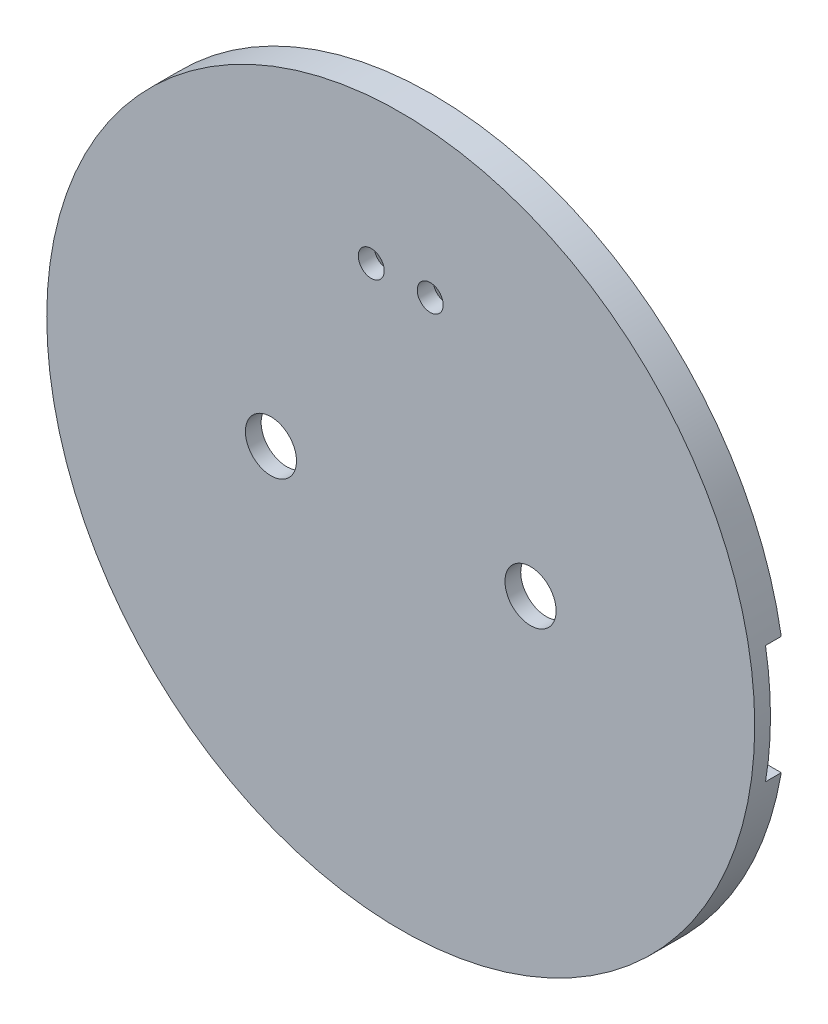
SolidWorks part; units mm, degrees
ref_plane "Plano frontal" through (0, 0, 0) normal (0, 0, 1) x (1, 0, 0)
ref_plane "Plano superior" through (0, 0, 0) normal (0, 1, 0) x (1, 0, 0)
ref_plane "Plano direito" through (0, 0, 0) normal (1, 0, 0) x (0, 0, -1)
sketch "Esboço1" plane through (0, 0, 0) normal (0, 0, 1) x (1, 0, 0)
  circle A0 centre (0, 0) radius 90
base flange "Flange-base2" sketch "Esboço1" thickness 8 reverse thickness direction no parameters "D1"=4
sketch "Esboço12" plane through (0, 0, -8) normal (0, 0, -1) x (-1, 0, 0)
  line L5 (-88.7412, 15) -> (88.7412, 15)
  line L6 (-88.7412, -15) -> (88.7412, -15)
  circle A0 centre (0, 0) radius 90 construction
  arc A1 (-88.7412, 15) -> (-88.7412, -15) centre (0, 0) ccw
  arc A2 (88.7412, 15) -> (88.7412, -15) centre (0, 0) cw
  point P0 (0, 0)
  point P4 (0, 0)
  point P11 (0, -15)
  point P14 (0, 15)
extrude "Corte-extrusão3" cut sketch "Esboço12" against normal blind 4 normal cut yes
sketch "Esboço13" plane through (0, 0, -4) normal (0, 0, -1) x (-1, 0, 0)
  circle A0 centre (33, 0) radius 6.5 construction
  circle A1 centre (-33, 0) radius 6.5 construction
  circle A2 centre (33, 0) radius 6.5
  circle A3 centre (-33, 0) radius 6.5
extrude "Corte-extrusão4" cut sketch "Esboço13" against normal blind 4 normal cut yes
sketch "Esboço18" plane through (0, 0, -8) normal (0, 0, -1) x (-1, 0, 0)
  line L0 (-7.5, 56) -> (-7.5, 50) construction
  line L1 (7.5, 56) -> (7.5, 50) construction
  point P6 (7.5, 53)
  point P8 (-7.5, 53)
hole_wizard "Escareado para parafuso Allen sextavado escareado de M63" positions "Esboço18" profile "Esboço19" countersink size "M6" standard "ISO" end condition through all
sketch "Esboço19" plane through (7.5, 53, -8) normal (1, 0, 0) x (0, 1, 0)
  line L0 (0, 0) -> (0, 8)
  line L1 (0, 8) -> (3.3, 8)
  line L2 (3.3, 8) -> (3.3, 3.92)
  line L3 (3.3, 3.92) -> (7.22, 0)
  line L5 (7.22, 0) -> (0, 0)
  line L6 (-3.3, 3.92) -> (-7.22, 0) construction
  line L11 (0, -6.35) -> (0, 107.95) construction
  dimension "Thru Hole Dia." = 6.6
  dimension "Thru Hole Depth" = 8
  dimension "Near C'Sink Dia." = 14.44
  dimension "Near C'Sink Angle" = 90
sketch "Curva-Linhas3" [suppressed] plane through (0, 0, 0) normal (0, 1, 0) x (1, 0, 0)
sketch "Caixa delimitadora3" [suppressed] plane through (0, 0, 0) normal (0, 1, 0) x (1, 0, 0)
sheet metal parameters "Chapa metálica2" thickness 8 parameters "D1"=4
flat pattern "Padrão-Plano2" [suppressed]
sketch "Curva-Linhas4" plane through (0, 0, 0) normal (0, 1, 0) x (1, 0, 0)
sketch "Caixa delimitadora4" [suppressed] plane through (0, 0, 0) normal (0, 1, 0) x (1, 0, 0)
sheet metal parameters "Chapa metálica3" thickness 8 parameters "D1"=4
flat pattern "Padrão-Plano2"
sketch "Curva-Linhas4" plane through (0, 0, 0) normal (0, 1, 0) x (1, 0, 0)
sketch3d "Caixa delimitadora4" [suppressed]
  line L0 (-89.9899, -90.01, 0) -> (90.0101, -89.9898, 0) construction
  line L1 (-90.0101, 89.9898, 0) -> (89.9899, 90.01, 0) construction
  line L2 (-89.9899, -90.01, 0) -> (-90.0101, 89.9898, 0) construction
  line L3 (90.0101, -89.9898, 0) -> (89.9899, 90.01, 0) construction
sheet metal parameters "Chapa metálica4" thickness 8 parameters "D1"=4
flat pattern "Padrão-Plano2"
sketch "Curva-Linhas4" plane through (0, 0, 0) normal (0, 1, 0) x (1, 0, 0)
sketch3d "Caixa delimitadora4" [suppressed]
  line L0 (-89.9899, -90.01, 0) -> (90.0101, -89.9898, 0) construction
  line L1 (-90.0101, 89.9898, 0) -> (89.9899, 90.01, 0) construction
  line L2 (-89.9899, -90.01, 0) -> (-90.0101, 89.9898, 0) construction
  line L3 (90.0101, -89.9898, 0) -> (89.9899, 90.01, 0) construction
sheet metal parameters "Chapa metálica7" thickness 8 parameters "D1"=4
flat pattern "Padrão-Plano2"
sketch "Curva-Linhas4" plane through (0, 0, 0) normal (0, 1, 0) x (1, 0, 0)
sketch3d "Caixa delimitadora4" [suppressed]
  line L0 (-89.9899, -90.01, 0) -> (90.0101, -89.9898, 0) construction
  line L1 (-90.0101, 89.9898, 0) -> (89.9899, 90.01, 0) construction
  line L2 (-89.9899, -90.01, 0) -> (-90.0101, 89.9898, 0) construction
  line L3 (90.0101, -89.9898, 0) -> (89.9899, 90.01, 0) construction
